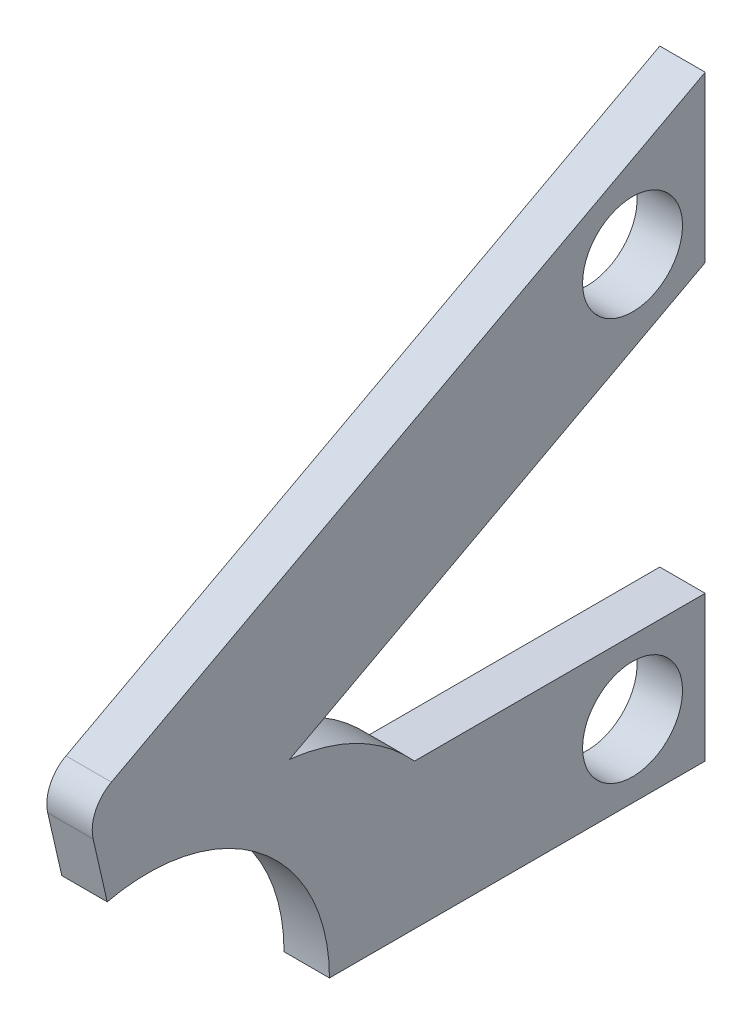
SolidWorks part; units mm, degrees
ref_plane "Front Plane" through (0, 0, 0) normal (0, 0, 1) x (1, 0, 0)
ref_plane "Top Plane" through (0, 0, 0) normal (0, 1, 0) x (1, 0, 0)
ref_plane "Right Plane" through (0, 0, 0) normal (1, 0, 0) x (0, 0, -1)
sketch "Sketch2" plane through (-112.555, 0, -573.5897) normal (-1, 0, 0) x (0, 0.6231, 0.7821)
  line L0 (843.7852, 138.5824) -> (864.3306, 122.2137)
  line L1 (871.0899, 172.8543) -> (811.2713, 97.7721) construction
  line L2 (864.3306, 122.2137) -> (884.1965, 122.2137) construction
  line L3 (884.1965, 122.2137) -> (887.6455, 124.9615)
  line L4 (850.1161, 146.5287) -> (866.0089, 133.8669)
  line L5 (888.3957, 127.9526) -> (869.774, 171.2026)
  line L6 (875.6249, 131.922) -> (862.593, 162.1893)
  line L7 (843.7852, 138.5824) -> (850.1161, 146.5287)
  line L8 (862.593, 162.1893) -> (869.774, 171.2026)
  circle A0 centre (874.2635, 114.3) radius 12.7 construction
  arc A1 (864.3306, 122.2137) -> (884.1965, 122.2137) centre (874.2635, 114.3) cw
  arc A2 (887.6455, 124.9615) -> (888.3957, 127.9526) centre (886.0628, 126.9481) ccw
  spline S0 degree 2 poles (866.0089, 133.8669) (871.1832, 134.6851) (875.6249, 131.922) knots 0 0 0 1 1 1
  point P17 (889.163, 126.1705)
  point P18 (0, 0)
  dimension "D5" = 2.54
  dimension "D1" = 10.16
  dimension "D2" = 10.16
  dimension "D3" = 6.35
  dimension "D4" = 20.32
extrude "Boss-Extrude1" add sketch "Sketch2" along normal blind 3.175 contours L4 S0 L6 L8 L5 A2 L3 A1 L0 L7
sketch "Sketch7" plane through (-115.73, 0, 0) normal (-1, 0, 0) x (0, 0, 1)
  line L0 (0, 644.3314) -> (20.32, 644.3314) construction
  line L1 (0, 634.1714) -> (0, 644.3314) construction
  line L2 (41.5146, 653.6555) -> (0, 675.8787) construction
  line L3 (0, 664.3546) -> (0, 675.8787) construction
  circle A0 centre (5.08, 639.2514) radius 3.4925
  circle A1 centre (5.08, 667.3973) radius 3.4925
  dimension "D1" = 5.08
  dimension "D2" = 5.08
  dimension "D3" = 5.08
  dimension "D4" = 5.08
extrude "Cut-Extrude3" cut sketch "Sketch7" against normal through all
